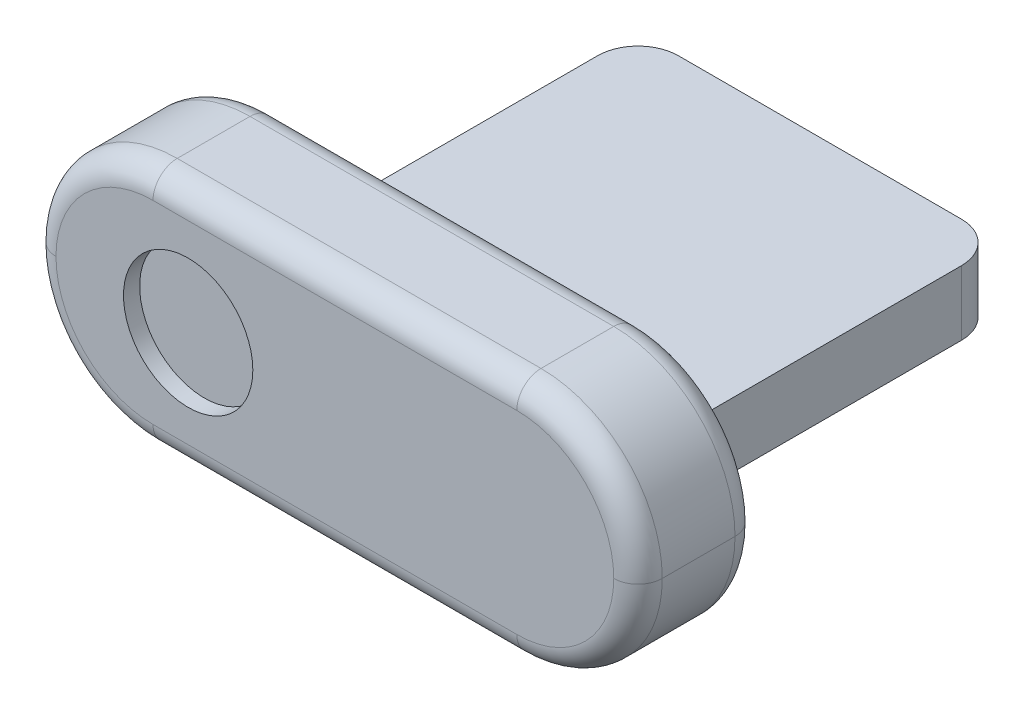
SolidWorks part; units mm, degrees
ref_plane "Front Plane" through (0, 0, 0) normal (0, 0, 1) x (1, 0, 0)
ref_plane "Top Plane" through (0, 0, 0) normal (0, 1, 0) x (1, 0, 0)
ref_plane "Right Plane" through (0, 0, 0) normal (1, 0, 0) x (0, 0, -1)
sketch "Sketch1" plane through (0, 0, 0) normal (0, 0, 1) x (1, 0, 0)
  line L0 (-40, -3) -> (-40, 40.3751) construction
  line L1 (12, -3) -> (-92, -3) construction
  line L3 (-77.5, 38.5298) -> (-2.5, 38.5298)
  line L4 (-77.5, 38.5298) -> (-77.5, 8.5298)
  line L5 (-77.5, 8.5298) -> (-2.5, 8.5298)
  line L6 (-2.5, 38.5298) -> (-2.5, 8.5298)
  dimension "D1" = 75
  dimension "D2" = 30
  dimension "D3" = 37.5
extrude "Boss-Extrude1" add sketch "Sketch1" against normal blind 15
fillet "Fillet1" radius 15 4 edges at (-77.5, 8.5298, -7.5) (-77.5, 38.5298, -7.5) (-2.5, 8.5298, -7.5) (-2.5, 38.5298, -7.5)
sketch "Sketch2" plane through (0, 0, -15) normal (0, 0, -1) x (-1, 0, 0)
  line L0 (17.5, 38.5298) -> (62.5, 38.5298) construction
  line L1 (17.5, 23.5298) -> (62.5, 23.5298)
  line L2 (17.5, 23.5298) -> (17.5, 15.5298)
  line L3 (17.5, 15.5298) -> (62.5, 15.5298)
  line L4 (62.5, 23.5298) -> (62.5, 15.5298)
  dimension "D1" = 15
  dimension "D2" = 15
  dimension "D3" = 8
  dimension "D4" = 15
extrude "Boss-Extrude2" add sketch "Sketch2" along normal blind 45 contours L1 L4 L3 L2
fillet "Fillet2" radius 5 2 edges at (-62.5, 19.5298, -60) (-17.5, 19.5298, -60)
fillet "Fillet3" radius 3 12 edges at (-6.8934, 34.1364, -15) (-6.8934, 12.9232, -15) (-40, 8.5298, -15) (-73.1066, 12.9232, -15) (-73.1066, 34.1364, -15) (-6.8934, 34.1364, 0) (-6.8934, 12.9232, 0) (-40, 8.5298, 0) (-73.1066, 12.9232, 0) (-73.1066, 34.1364, 0) (-40, 38.5298, -15) (-40, 38.5298, 0)
sketch "Sketch3" plane through (0, 0, 0) normal (0, 0, 1) x (1, 0, 0)
  circle A0 centre (-58.1484, 23.5298) radius 8
extrude "Cut-Extrude1" cut sketch "Sketch3" against normal blind 2
